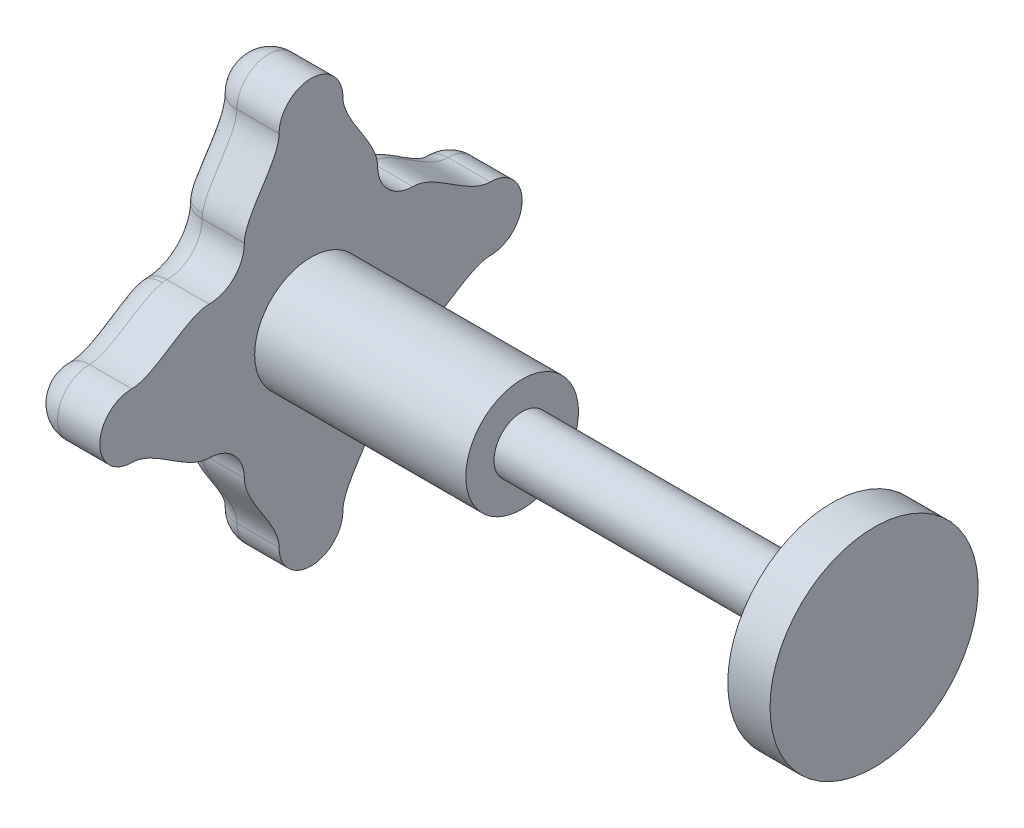
SolidWorks part; units mm, degrees
material "ABS"
ref_plane "Plan de face" through (0, 0, 0) normal (0, 0, 1) x (1, 0, 0)
ref_plane "Plan de dessus" through (0, 0, 0) normal (0, 1, 0) x (1, 0, 0)
ref_plane "Plan de droite" through (0, 0, 0) normal (1, 0, 0) x (0, 0, -1)
sketch "Esquisse1" plane through (0, 0, 0) normal (0, 0, 1) x (1, 0, 0)
  line L0 (0, 0) -> (36.4532, 0) construction
  line L1 (28.1745, 0) -> (28.1745, 7.3934)
  line L2 (28.1745, 7.3934) -> (25.1745, 7.3934)
  line L3 (25.1745, 7.3934) -> (25.1745, 1)
  line L4 (25.1745, 1) -> (23.1745, 1)
  line L5 (23.1745, 1) -> (23.1745, 2)
  line L6 (23.1745, 2) -> (3.1745, 2)
  line L7 (3.1745, 2) -> (3.1745, 4)
  line L8 (3.1745, 4) -> (-11.8255, 4)
  line L9 (-11.8255, 4) -> (-11.8255, 15)
  line L10 (-11.8255, 15) -> (-16.8255, 15)
  line L11 (-16.8255, 15) -> (-16.8255, 0)
  line L12 (28.1745, 0) -> (-16.8255, 0)
  dimension "D1" = 5
  dimension "D2" = 2
  dimension "D3" = 3
  dimension "D4" = 1
  dimension "D5" = 2
  dimension "D6" = 2
  dimension "D7" = 15
  dimension "D8" = 15
  dimension "D9" = 20
revolve "Révolution1" add sketch "Esquisse1" angle 360 about L0
sketch "Esquisse2" plane through (-16.8255, 0, 0) normal (-1, 0, 0) x (0, 0, 1)
  line L0 (0, 0) -> (0, 12.7316) construction
  line L1 (0, 0) -> (-7.232, 7.232) construction
  arc A0 (2.2684, 12.7316) -> (-2.2684, 12.7316) centre (0, 12.7316) ccw
  arc A1 (-7.232, 4.732) -> (-4.732, 7.232) centre (-7.232, 7.232) ccw
  circle A2 centre (0, 0) radius 15 construction
  arc A3 (12.7316, -2.2684) -> (12.7316, 2.2684) centre (12.7316, 0) ccw
  arc A4 (4.732, 7.232) -> (7.232, 4.732) centre (7.232, 7.232) ccw
  arc A5 (-2.2684, -12.7316) -> (2.2684, -12.7316) centre (0, -12.7316) ccw
  arc A6 (7.232, -4.732) -> (4.732, -7.232) centre (7.232, -7.232) ccw
  arc A7 (-12.7316, 2.2684) -> (-12.7316, -2.2684) centre (-12.7316, 0) ccw
  arc A8 (-4.732, -7.232) -> (-7.232, -4.732) centre (-7.232, -7.232) ccw
  circle A9 centre (0, 0) radius 15
  spline S0 degree 3 poles (-4.732, 7.232) (-4.732, 8.8897) (-2.2684, 11.0725) (-2.2684, 12.7316) knots 0 0 0 0 1 1 1 1
  spline S1 degree 3 poles (4.732, 7.232) (4.732, 8.8897) (2.2684, 11.0725) (2.2684, 12.7316) knots 0 0 0 0 1 1 1 1
  spline S2 degree 3 poles (7.232, -4.732) (8.8897, -4.732) (11.0725, -2.2684) (12.7316, -2.2684) knots 0 0 0 0 1 1 1 1
  spline S3 degree 3 poles (7.232, 4.732) (8.8897, 4.732) (11.0725, 2.2684) (12.7316, 2.2684) knots 0 0 0 0 1 1 1 1
  spline S4 degree 3 poles (-4.732, -7.232) (-4.732, -8.8897) (-2.2684, -11.0725) (-2.2684, -12.7316) knots 0 0 0 0 1 1 1 1
  spline S5 degree 3 poles (4.732, -7.232) (4.732, -8.8897) (2.2684, -11.0725) (2.2684, -12.7316) knots 0 0 0 0 1 1 1 1
  spline S6 degree 3 poles (-7.232, 4.732) (-8.8897, 4.732) (-11.0725, 2.2684) (-12.7316, 2.2684) knots 0 0 0 0 1 1 1 1
  spline S7 degree 3 poles (-7.232, -4.732) (-8.8897, -4.732) (-11.0725, -2.2684) (-12.7316, -2.2684) knots 0 0 0 0 1 1 1 1
  point P39 (0, 0)
  circle M20 centre (0, 0) radius 15
  dimension "D2" = 5
  dimension "D1" = 45
  dimension "D3" = 4
extrude "Enlèv. mat.-Extru.1" cut sketch "Esquisse2" against normal up to next contours S6 A1 S0 A0 A7 M20 | A4 S3 A3 A0 S1 M20 | A6 S5 A5 A3 S2 M20 | A8 S7 A7 A5 S4 M20
fillet "Congé1" radius 2 8 edges at (-16.8255, 5.4642, 5.4642) (-16.8255, 15, 0) (-16.8255, 5.4642, -5.4642) (-16.8255, 0, -15) (-16.8255, -5.4642, -5.4642) (-16.8255, -15, 0) (-16.8255, -5.4642, 5.4642) (-16.8255, 0, 15)
